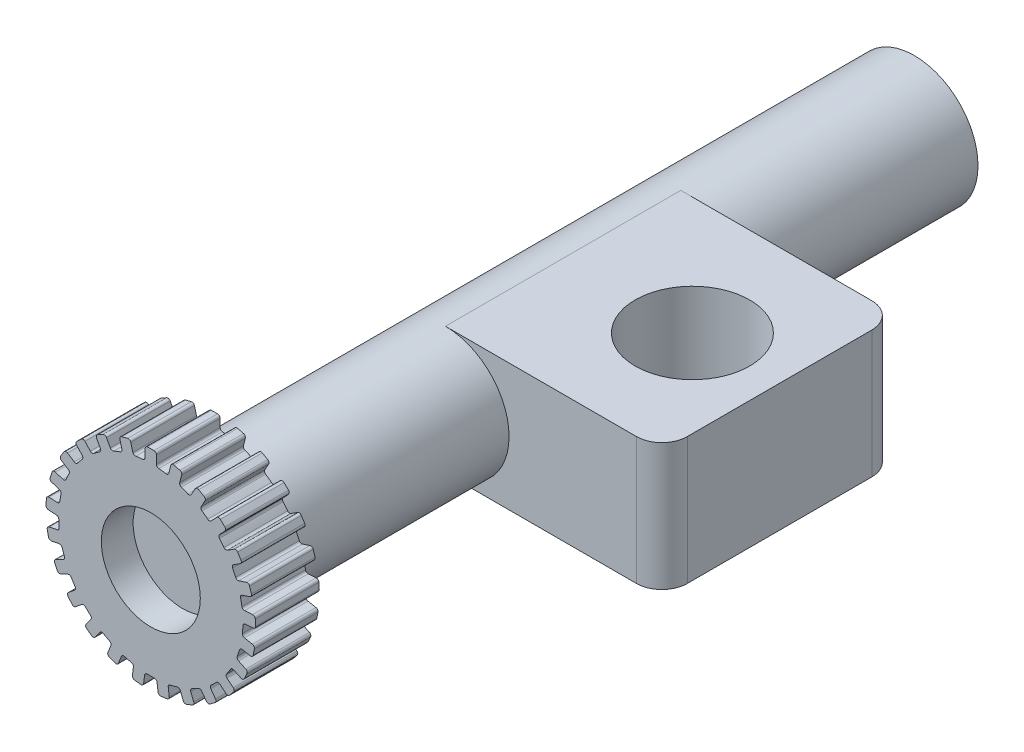
SolidWorks part; units mm, degrees
ref_plane "Front Plane" through (0, 0, 0) normal (0, 0, 1) x (1, 0, 0)
ref_plane "Top Plane" through (0, 0, 0) normal (0, 1, 0) x (1, 0, 0)
ref_plane "Right Plane" through (0, 0, 0) normal (1, 0, 0) x (0, 0, -1)
sketch "Sketch1" plane through (0, 0, 0) normal (0, 0, 1) x (1, 0, 0)
  circle A0 centre (0, 0) radius 5
  dimension "D1" = 10
extrude "Boss-Extrude1" add sketch "Sketch1" along normal blind 55
sketch "Sketch2" plane through (0, 0, 55) normal (0, 0, 1) x (1, 0, 0)
  line L0 (2.4285, 7.6744) -> (2.2719, 7.0646)
  line L1 (-0.2436, 8.2372) -> (0.2436, 8.2372)
  line L2 (0.4436, 8.0372) -> (0.4436, 7.4077)
  line L3 (-0.4436, 8.0372) -> (-0.4436, 7.4077)
  line L4 (1.5691, 7.8951) -> (1.4125, 7.2853)
  line L5 (1.8125, 8.039) -> (2.2845, 7.9179)
  line L6 (4.2607, 6.8294) -> (3.9574, 6.2777)
  line L7 (3.4832, 7.2568) -> (3.1799, 6.7051)
  line L8 (3.7548, 7.3357) -> (4.1818, 7.101)
  line L9 (5.8253, 5.5552) -> (5.3943, 5.0963)
  line L10 (5.1785, 6.1626) -> (4.7475, 5.7036)
  line L11 (5.4612, 6.1715) -> (5.8164, 5.8379)
  line L12 (7.0238, 3.932) -> (6.4922, 3.5947)
  line L13 (6.5484, 4.6811) -> (6.0168, 4.3438)
  line L14 (6.8244, 4.6194) -> (7.0855, 4.208)
  line L15 (7.781, 2.0617) -> (7.1822, 1.8672)
  line L16 (7.5068, 2.9056) -> (6.908, 2.711)
  line L17 (7.7588, 2.7771) -> (7.9094, 2.3137)
  line L18 (8.0492, 0.0619) -> (7.4209, 0.0224)
  line L19 (7.9935, 0.9474) -> (7.3652, 0.9079)
  line L20 (8.2057, 0.7604) -> (8.2363, 0.2741)
  line L21 (7.8118, -1.9418) -> (7.1933, -1.8238)
  line L22 (7.978, -1.0703) -> (7.3596, -0.9523)
  line L23 (8.137, -1.3042) -> (8.0457, -1.7828)
  line L24 (7.0834, -3.8235) -> (6.5138, -3.5554)
  line L25 (7.4612, -3.0207) -> (6.8915, -2.7526)
  line L26 (7.557, -3.2868) -> (7.3495, -3.7277)
  line L27 (5.91, -5.4649) -> (5.4249, -5.0636)
  line L28 (6.4756, -4.7813) -> (5.9905, -4.38)
  line L29 (6.5022, -5.0629) -> (6.1916, -5.4383)
  line L30 (4.3653, -6.763) -> (3.9952, -6.2537)
  line L31 (5.0831, -6.2415) -> (4.713, -5.7322)
  line L32 (5.0388, -6.5209) -> (4.6446, -6.8073)
  line L33 (2.5462, -7.6361) -> (2.3145, -7.0508)
  line L34 (3.3712, -7.3095) -> (3.1394, -6.7242)
  line L35 (3.2588, -7.5691) -> (2.8058, -7.7485)
  line L36 (0.5672, -8.0295) -> (0.4883, -7.4048)
  line L37 (1.4475, -7.9183) -> (1.3686, -7.2936)
  line L38 (1.2741, -8.1418) -> (0.7907, -8.2028)
  line L39 (-1.4475, -7.9183) -> (-1.3686, -7.2936)
  line L40 (-0.5672, -8.0295) -> (-0.4883, -7.4048)
  line L41 (-0.7907, -8.2028) -> (-1.2741, -8.1418)
  line L42 (-3.3712, -7.3095) -> (-3.1394, -6.7242)
  line L43 (-2.5462, -7.6361) -> (-2.3145, -7.0508)
  line L44 (-2.8058, -7.7485) -> (-3.2588, -7.5691)
  line L45 (-5.0831, -6.2415) -> (-4.713, -5.7322)
  line L46 (-4.3653, -6.763) -> (-3.9952, -6.2537)
  line L47 (-4.6446, -6.8073) -> (-5.0388, -6.5209)
  line L48 (-6.4756, -4.7813) -> (-5.9905, -4.38)
  line L49 (-5.91, -5.4649) -> (-5.4249, -5.0636)
  line L50 (-6.1916, -5.4383) -> (-6.5022, -5.0629)
  line L51 (-7.4612, -3.0207) -> (-6.8915, -2.7526)
  line L52 (-7.0834, -3.8235) -> (-6.5138, -3.5554)
  line L53 (-7.3495, -3.7277) -> (-7.557, -3.2868)
  line L54 (-7.978, -1.0703) -> (-7.3596, -0.9523)
  line L55 (-7.8118, -1.9418) -> (-7.1933, -1.8238)
  line L56 (-8.0457, -1.7828) -> (-8.137, -1.3042)
  line L57 (-7.9935, 0.9474) -> (-7.3652, 0.9079)
  line L58 (-8.0492, 0.0619) -> (-7.4209, 0.0224)
  line L59 (-8.2363, 0.2741) -> (-8.2057, 0.7604)
  line L60 (-7.5068, 2.9056) -> (-6.908, 2.711)
  line L61 (-7.781, 2.0617) -> (-7.1822, 1.8672)
  line L62 (-7.9094, 2.3137) -> (-7.7588, 2.7771)
  line L63 (-6.5484, 4.6811) -> (-6.0168, 4.3438)
  line L64 (-7.0238, 3.932) -> (-6.4922, 3.5947)
  line L65 (-7.0855, 4.208) -> (-6.8244, 4.6194)
  line L66 (-5.1785, 6.1626) -> (-4.7475, 5.7036)
  line L67 (-5.8253, 5.5552) -> (-5.3943, 5.0963)
  line L68 (-5.8164, 5.8379) -> (-5.4612, 6.1715)
  line L69 (-3.4832, 7.2568) -> (-3.1799, 6.7051)
  line L70 (-4.2607, 6.8294) -> (-3.9574, 6.2777)
  line L71 (-4.1818, 7.101) -> (-3.7548, 7.3357)
  line L72 (-1.5691, 7.8951) -> (-1.4125, 7.2853)
  line L73 (-2.4285, 7.6744) -> (-2.2719, 7.0646)
  line L74 (-2.2845, 7.9179) -> (-1.8125, 8.039)
  arc A0 (-0.6263, 7.2084) -> (-1.186, 7.1377) centre (0, 0) ccw
  arc A2 (0.4436, 8.0372) -> (0.2436, 8.2372) centre (0.2436, 8.0372) ccw
  arc A3 (-0.2436, 8.2372) -> (-0.4436, 8.0372) centre (-0.2436, 8.0372) ccw
  arc A4 (-0.6263, 7.2084) -> (-0.4436, 7.4077) centre (-0.6436, 7.4077) ccw
  arc A5 (0.6263, 7.2084) -> (0.4436, 7.4077) centre (0.6436, 7.4077) cw
  arc A6 (1.8125, 8.039) -> (1.5691, 7.8951) centre (1.7628, 7.8453) ccw
  arc A7 (2.4285, 7.6744) -> (2.2845, 7.9179) centre (2.2348, 7.7241) ccw
  arc A8 (1.186, 7.1377) -> (1.4125, 7.2853) centre (1.2188, 7.335) ccw
  arc A9 (2.3993, 6.8262) -> (2.2719, 7.0646) centre (2.4656, 7.0149) cw
  arc A10 (3.7548, 7.3357) -> (3.4832, 7.2568) centre (3.6585, 7.1605) ccw
  arc A11 (4.2607, 6.8294) -> (4.1818, 7.101) centre (4.0855, 6.9257) ccw
  arc A12 (2.9238, 6.6185) -> (3.1799, 6.7051) centre (3.0047, 6.8014) ccw
  arc A13 (4.0215, 6.015) -> (3.9574, 6.2777) centre (4.1327, 6.1813) cw
  arc A14 (5.4612, 6.1715) -> (5.1785, 6.1626) centre (5.3243, 6.0257) ccw
  arc A15 (5.8253, 5.5552) -> (5.8164, 5.8379) centre (5.6795, 5.6921) ccw
  arc A16 (4.4779, 5.6834) -> (4.7475, 5.7036) centre (4.6017, 5.8405) ccw
  arc A17 (5.3911, 4.826) -> (5.3943, 5.0963) centre (5.5401, 4.9594) cw
  arc A18 (6.8244, 4.6194) -> (6.5484, 4.6811) centre (6.6555, 4.5123) ccw
  arc A19 (7.0238, 3.932) -> (7.0855, 4.208) centre (6.9166, 4.1009) ccw
  arc A20 (5.7507, 4.3913) -> (6.0168, 4.3438) centre (5.9096, 4.5127) ccw
  arc A21 (6.4219, 3.3336) -> (6.4922, 3.5947) centre (6.5994, 3.4258) cw
  arc A22 (7.7588, 2.7771) -> (7.5068, 2.9056) centre (7.5686, 2.7153) ccw
  arc A23 (7.781, 2.0617) -> (7.9094, 2.3137) centre (7.7192, 2.2519) ccw
  arc A24 (6.6621, 2.8232) -> (6.908, 2.711) centre (6.8462, 2.9012) ccw
  arc A25 (7.0491, 1.6319) -> (7.1822, 1.8672) centre (7.244, 1.677) cw
  arc A26 (8.2057, 0.7604) -> (7.9935, 0.9474) centre (8.0061, 0.7478) ccw
  arc A27 (8.0492, 0.0619) -> (8.2363, 0.2741) centre (8.0367, 0.2615) ccw
  arc A28 (7.1549, 1.0777) -> (7.3652, 0.9079) centre (7.3526, 1.1075) ccw
  arc A29 (7.2335, -0.1725) -> (7.4209, 0.0224) centre (7.4335, -0.1772) cw
  arc A30 (8.137, -1.3042) -> (7.978, -1.0703) centre (7.9405, -1.2667) ccw
  arc A31 (7.8118, -1.9418) -> (8.0457, -1.7828) centre (7.8492, -1.7453) ccw
  arc A32 (7.1981, -0.7355) -> (7.3596, -0.9523) centre (7.3971, -0.7558) ccw
  arc A33 (6.9634, -1.9659) -> (7.1933, -1.8238) centre (7.1558, -2.0203) cw
  arc A34 (7.557, -3.2868) -> (7.4612, -3.0207) centre (7.376, -3.2017) ccw
  arc A35 (7.0834, -3.8235) -> (7.3495, -3.7277) centre (7.1686, -3.6425) ccw
  arc A36 (6.789, -2.5025) -> (6.8915, -2.7526) centre (6.9767, -2.5717) ccw
  arc A37 (6.2557, -3.6359) -> (6.5138, -3.5554) centre (6.4286, -3.7364) cw
  arc A38 (6.5022, -5.0629) -> (6.4756, -4.7813) centre (6.3481, -4.9354) ccw
  arc A39 (5.91, -5.4649) -> (6.1916, -5.4383) centre (6.0375, -5.3108) ccw
  arc A40 (5.9534, -4.1122) -> (5.9905, -4.38) centre (6.118, -4.2259) ccw
  arc A41 (5.1549, -5.0774) -> (5.4249, -5.0636) centre (5.2974, -5.2177) cw
  arc A42 (5.0388, -6.5209) -> (5.0831, -6.2415) centre (4.9213, -6.3591) ccw
  arc A43 (4.3653, -6.763) -> (4.6446, -6.8073) centre (4.5271, -6.6455) ccw
  arc A44 (4.7437, -5.4636) -> (4.713, -5.7322) centre (4.8748, -5.6146) ccw
  arc A45 (3.7303, -6.1999) -> (3.9952, -6.2537) centre (3.8334, -6.3712) cw
  arc A46 (3.2588, -7.5691) -> (3.3712, -7.3095) centre (3.1852, -7.3832) ccw
  arc A47 (2.5462, -7.6361) -> (2.8058, -7.7485) centre (2.7322, -7.5625) ccw
  arc A48 (3.2359, -6.4716) -> (3.1394, -6.7242) centre (3.3254, -6.6505) ccw
  arc A49 (2.0713, -6.9328) -> (2.3145, -7.0508) centre (2.1285, -7.1244) cw
  arc A50 (1.2741, -8.1418) -> (1.4475, -7.9183) centre (1.249, -7.9433) ccw
  arc A51 (0.5672, -8.0295) -> (0.7907, -8.2028) centre (0.7656, -8.0044) ccw
  arc A52 (1.5248, -7.0731) -> (1.3686, -7.2936) centre (1.567, -7.2686) ccw
  arc A53 (0.2821, -7.2301) -> (0.4883, -7.4048) centre (0.2899, -7.4299) cw
  arc A54 (-0.7907, -8.2028) -> (-0.5672, -8.0295) centre (-0.7656, -8.0044) ccw
  arc A55 (-1.4475, -7.9183) -> (-1.2741, -8.1418) centre (-1.249, -7.9433) ccw
  arc A56 (-0.2821, -7.2301) -> (-0.4883, -7.4048) centre (-0.2899, -7.4299) ccw
  arc A57 (-1.5248, -7.0731) -> (-1.3686, -7.2936) centre (-1.567, -7.2686) cw
  arc A58 (-2.8058, -7.7485) -> (-2.5462, -7.6361) centre (-2.7322, -7.5625) ccw
  arc A59 (-3.3712, -7.3095) -> (-3.2588, -7.5691) centre (-3.1852, -7.3832) ccw
  arc A60 (-2.0713, -6.9328) -> (-2.3145, -7.0508) centre (-2.1285, -7.1244) ccw
  arc A61 (-3.2359, -6.4716) -> (-3.1394, -6.7242) centre (-3.3254, -6.6505) cw
  arc A62 (-4.6446, -6.8073) -> (-4.3653, -6.763) centre (-4.5271, -6.6455) ccw
  arc A63 (-5.0831, -6.2415) -> (-5.0388, -6.5209) centre (-4.9213, -6.3591) ccw
  arc A64 (-3.7303, -6.1999) -> (-3.9952, -6.2537) centre (-3.8334, -6.3712) ccw
  arc A65 (-4.7437, -5.4636) -> (-4.713, -5.7322) centre (-4.8748, -5.6146) cw
  arc A66 (-6.1916, -5.4383) -> (-5.91, -5.4649) centre (-6.0375, -5.3108) ccw
  arc A67 (-6.4756, -4.7813) -> (-6.5022, -5.0629) centre (-6.3481, -4.9354) ccw
  arc A68 (-5.1549, -5.0774) -> (-5.4249, -5.0636) centre (-5.2974, -5.2177) ccw
  arc A69 (-5.9534, -4.1122) -> (-5.9905, -4.38) centre (-6.118, -4.2259) cw
  arc A70 (-7.3495, -3.7277) -> (-7.0834, -3.8235) centre (-7.1686, -3.6425) ccw
  arc A71 (-7.4612, -3.0207) -> (-7.557, -3.2868) centre (-7.376, -3.2017) ccw
  arc A72 (-6.2557, -3.6359) -> (-6.5138, -3.5554) centre (-6.4286, -3.7364) ccw
  arc A73 (-6.789, -2.5025) -> (-6.8915, -2.7526) centre (-6.9767, -2.5717) cw
  arc A74 (-8.0457, -1.7828) -> (-7.8118, -1.9418) centre (-7.8492, -1.7453) ccw
  arc A75 (-7.978, -1.0703) -> (-8.137, -1.3042) centre (-7.9405, -1.2667) ccw
  arc A76 (-6.9634, -1.9659) -> (-7.1933, -1.8238) centre (-7.1558, -2.0203) ccw
  arc A77 (-7.1981, -0.7355) -> (-7.3596, -0.9523) centre (-7.3971, -0.7558) cw
  arc A78 (-8.2363, 0.2741) -> (-8.0492, 0.0619) centre (-8.0367, 0.2615) ccw
  arc A79 (-7.9935, 0.9474) -> (-8.2057, 0.7604) centre (-8.0061, 0.7478) ccw
  arc A80 (-7.2335, -0.1725) -> (-7.4209, 0.0224) centre (-7.4335, -0.1772) ccw
  arc A81 (-7.1549, 1.0777) -> (-7.3652, 0.9079) centre (-7.3526, 1.1075) cw
  arc A82 (-7.9094, 2.3137) -> (-7.781, 2.0617) centre (-7.7192, 2.2519) ccw
  arc A83 (-7.5068, 2.9056) -> (-7.7588, 2.7771) centre (-7.5686, 2.7153) ccw
  arc A84 (-7.0491, 1.6319) -> (-7.1822, 1.8672) centre (-7.244, 1.677) ccw
  arc A85 (-6.6621, 2.8232) -> (-6.908, 2.711) centre (-6.8462, 2.9012) cw
  arc A86 (-7.0855, 4.208) -> (-7.0238, 3.932) centre (-6.9166, 4.1009) ccw
  arc A87 (-6.5484, 4.6811) -> (-6.8244, 4.6194) centre (-6.6555, 4.5123) ccw
  arc A88 (-6.4219, 3.3336) -> (-6.4922, 3.5947) centre (-6.5994, 3.4258) ccw
  arc A89 (-5.7507, 4.3913) -> (-6.0168, 4.3438) centre (-5.9096, 4.5127) cw
  arc A90 (-5.8164, 5.8379) -> (-5.8253, 5.5552) centre (-5.6795, 5.6921) ccw
  arc A91 (-5.1785, 6.1626) -> (-5.4612, 6.1715) centre (-5.3243, 6.0257) ccw
  arc A92 (-5.3911, 4.826) -> (-5.3943, 5.0963) centre (-5.5401, 4.9594) ccw
  arc A93 (-4.4779, 5.6834) -> (-4.7475, 5.7036) centre (-4.6017, 5.8405) cw
  arc A94 (-4.1818, 7.101) -> (-4.2607, 6.8294) centre (-4.0855, 6.9257) ccw
  arc A95 (-3.4832, 7.2568) -> (-3.7548, 7.3357) centre (-3.6585, 7.1605) ccw
  arc A96 (-4.0215, 6.015) -> (-3.9574, 6.2777) centre (-4.1327, 6.1813) ccw
  arc A97 (-2.9238, 6.6185) -> (-3.1799, 6.7051) centre (-3.0047, 6.8014) cw
  arc A98 (-2.2845, 7.9179) -> (-2.4285, 7.6744) centre (-2.2348, 7.7241) ccw
  arc A99 (-1.5691, 7.8951) -> (-1.8125, 8.039) centre (-1.7628, 7.8453) ccw
  arc A100 (-2.3993, 6.8262) -> (-2.2719, 7.0646) centre (-2.4656, 7.0149) ccw
  arc A101 (-1.186, 7.1377) -> (-1.4125, 7.2853) centre (-1.2188, 7.335) cw
  arc A102 (-2.3993, 6.8262) -> (-2.9238, 6.6185) centre (0, 0) ccw
  arc A103 (-4.0215, 6.015) -> (-4.4779, 5.6834) centre (0, 0) ccw
  arc A104 (-5.3911, 4.826) -> (-5.7507, 4.3913) centre (0, 0) ccw
  arc A105 (-6.4219, 3.3336) -> (-6.6621, 2.8232) centre (0, 0) ccw
  arc A106 (-7.0491, 1.6319) -> (-7.1549, 1.0777) centre (0, 0) ccw
  arc A107 (-7.2335, -0.1725) -> (-7.1981, -0.7355) centre (0, 0) ccw
  arc A108 (-6.9634, -1.9659) -> (-6.789, -2.5025) centre (0, 0) ccw
  arc A109 (-6.2557, -3.6359) -> (-5.9534, -4.1122) centre (0, 0) ccw
  arc A110 (-5.1549, -5.0774) -> (-4.7437, -5.4636) centre (0, 0) ccw
  arc A111 (-3.7303, -6.1999) -> (-3.2359, -6.4716) centre (0, 0) ccw
  arc A112 (-2.0713, -6.9328) -> (-1.5248, -7.0731) centre (0, 0) ccw
  arc A113 (1.5248, -7.0731) -> (2.0713, -6.9328) centre (0, 0) ccw
  arc A114 (-0.2821, -7.2301) -> (0.2821, -7.2301) centre (0, 0) ccw
  arc A115 (3.2359, -6.4716) -> (3.7303, -6.1999) centre (0, 0) ccw
  arc A116 (4.7437, -5.4636) -> (5.1549, -5.0774) centre (0, 0) ccw
  arc A117 (5.9534, -4.1122) -> (6.2557, -3.6359) centre (0, 0) ccw
  arc A118 (6.789, -2.5025) -> (6.9634, -1.9659) centre (0, 0) ccw
  arc A119 (1.186, 7.1377) -> (0.6263, 7.2084) centre (0, 0) ccw
  arc A120 (2.9238, 6.6185) -> (2.3993, 6.8262) centre (0, 0) ccw
  arc A121 (4.4779, 5.6834) -> (4.0215, 6.015) centre (0, 0) ccw
  arc A122 (5.7507, 4.3913) -> (5.3911, 4.826) centre (0, 0) ccw
  arc A123 (6.6621, 2.8232) -> (6.4219, 3.3336) centre (0, 0) ccw
  arc A124 (7.1549, 1.0777) -> (7.0491, 1.6319) centre (0, 0) ccw
  arc A125 (7.1981, -0.7355) -> (7.2335, -0.1725) centre (0, 0) ccw
  point P11 (0.4436, 8.2372)
  point P14 (-0.4436, 8.2372)
  point P308 (0, 0)
  dimension "D1" = 0.2
  dimension "D2" = 0.2
  dimension "D3" = 0.2
  dimension "D4" = 25
extrude "Boss-Extrude2" add sketch "Sketch2" along normal blind 5
sketch "Sketch3" plane through (0, 0, 0) normal (0, 1, 0) x (1, 0, 0)
  line L1 (5, -18.355) -> (0.7193, -18.355)
  line L2 (5, -55) -> (5, 0) construction
  line L4 (0.7193, -36.8493) -> (5, -36.8493)
  line L5 (15.0083, -18.355) -> (5, -18.355)
  line L6 (17.0083, -20.355) -> (17.0083, -34.8493)
  line L7 (15.0083, -36.8493) -> (5, -36.8493)
  line L8 (0, -27.6021) -> (0, -36.8493)
  line L9 (0, -36.8493) -> (0.7193, -36.8493)
  line L10 (0, -27.6021) -> (0, -18.355)
  line L11 (0, -18.355) -> (0.7193, -18.355)
  arc A0 (15.0083, -36.8493) -> (17.0083, -34.8493) centre (15.0083, -34.8493) ccw
  arc A1 (17.0083, -20.355) -> (15.0083, -18.355) centre (15.0083, -20.355) ccw
  point P11 (0, -27.6021)
  point P12 (0, -27.6021)
  dimension "D1" = 2
extrude "Boss-Extrude3" add sketch "Sketch3" along normal blind 5 and the other way blind 5
sketch "Sketch4" plane through (0, 5, 0) normal (0, 1, 0) x (1, 0, 0)
  circle A2 centre (10.1612, -27.6021) radius 4.5018
  point P12 (8.4798, -27.6021)
extrude "Cut-Extrude1" cut sketch "Sketch4" against normal blind 50
sketch "Sketch5" plane through (0, 0, 60) normal (0, 0, 1) x (1, 0, 0)
  circle A0 centre (0, 0) radius 3.8897
extrude "Cut-Extrude2" cut sketch "Sketch5" against normal blind 2.5
